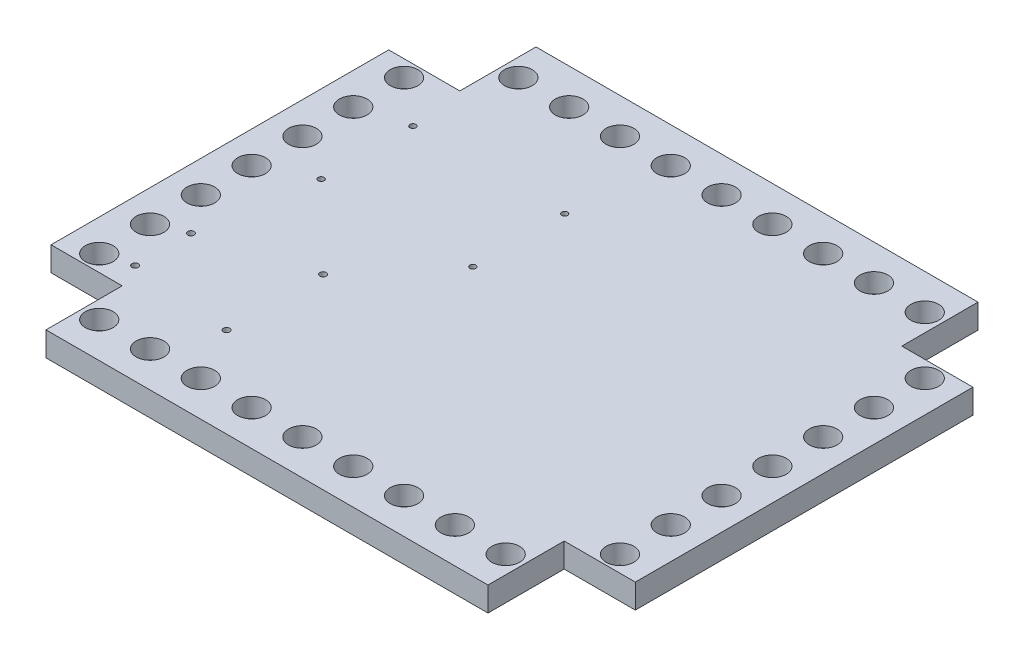
SolidWorks part; units mm, degrees
material "PA Type 6"
ref_plane "Front Plane" through (0, 0, 0) normal (0, 0, 1) x (1, 0, 0)
ref_plane "Top Plane" through (0, 0, 0) normal (0, 1, 0) x (1, 0, 0)
ref_plane "Right Plane" through (0, 0, 0) normal (1, 0, 0) x (0, 0, -1)
sketch "Sketch1" plane through (0, 0, 0) normal (0, 1, 0) x (1, 0, 0)
  line L1 (146.05, 122.5) -> (-146.05, 122.5)
  line L2 (146.05, 122.5) -> (146.05, -122.5)
  line L3 (146.05, -122.5) -> (-146.05, -122.5)
  line L4 (-146.05, 122.5) -> (-146.05, -122.5)
  line L5 (146.05, 122.5) -> (-146.05, -122.5) construction
  line L6 (146.05, -122.5) -> (-146.05, 122.5) construction
  point P0 (0, 0)
  dimension "D1" = 245
  dimension "D2" = 292.1
extrude "Boss-Extrude1" add sketch "Sketch1" along normal blind 9.652
sketch "Sketch2" plane through (0, 9.652, 0) normal (0, 1, 0) x (1, 0, 0)
  line L1 (146.05, 122.5) -> (-146.05, 122.5) construction
  line L2 (-146.05, 122.5) -> (-146.05, -122.5) construction
  line L3 (-146.05, 84.4) -> (-146.05, 122.5)
  line L4 (-146.05, 122.5) -> (-110.49, 122.5)
  line L5 (0, 122.5) -> (0, -122.5) construction
  line L6 (-146.05, -122.5) -> (146.05, -122.5) construction
  line L7 (-146.05, 0) -> (146.05, 0) construction
  line L8 (146.05, -122.5) -> (146.05, 122.5) construction
  line L9 (146.05, 84.4) -> (146.05, 122.5)
  line L11 (146.05, 122.5) -> (110.49, 122.5)
  line L13 (146.05, -122.5) -> (110.49, -122.5)
  line L14 (146.05, -84.4) -> (146.05, -122.5)
  line L15 (-146.05, -84.4) -> (-146.05, -122.5)
  line L17 (-146.05, -122.5) -> (-110.49, -122.5)
  line L18 (-110.49, 122.5) -> (-110.49, 84.4)
  line L19 (-110.49, 84.4) -> (-146.05, 84.4)
  line L20 (110.49, 122.5) -> (110.49, 84.4)
  line L21 (110.49, 84.4) -> (146.05, 84.4)
  line L22 (110.49, -84.4) -> (146.05, -84.4)
  line L23 (110.49, -122.5) -> (110.49, -84.4)
  line L24 (-110.49, -122.5) -> (-110.49, -84.4)
  line L25 (-110.49, -84.4) -> (-146.05, -84.4)
  dimension "D1" = 38.1
  dimension "D2" = 35.56
extrude "Cut-Extrude2" cut sketch "Sketch2" against normal through all
hole_wizard "35/64 (0.54688) Diameter Hole1" positions "Sketch5" profile "Sketch6" hole size "35/64" standard "ANSI Inch" end condition through all
sketch "Sketch5" plane through (0, 9.652, 0) normal (0, 1, 0) x (1, 0, 0)
  line L0 (0, 122.5) -> (0, 0) construction
  line L1 (110.49, 122.5) -> (-110.49, 122.5) construction
  line L2 (0, 0) -> (-146.05, 0) construction
  line L3 (-146.05, 84.4) -> (-146.05, -84.4) construction
  line L4 (0, 104.775) -> (-130.175, 104.775) construction
  line L5 (-130.175, 104.775) -> (-130.175, 0) construction
  point P21 (-25.4, 104.775)
  point P27 (0, 104.775)
  point P30 (-130.175, 0)
  point P35 (-50.8, 104.775)
  point P37 (-76.2, 104.775)
  point P48 (76.2, 104.775)
  point P49 (50.8, 104.775)
  point P50 (25.4, 104.775)
  point P51 (76.2, -104.775)
  point P52 (50.8, -104.775)
  point P53 (25.4, -104.775)
  point P54 (0, -104.775)
  point P55 (-25.4, -104.775)
  point P56 (-50.8, -104.775)
  point P57 (-76.2, -104.775)
  point P60 (-130.175, 25.4)
  point P62 (-130.175, 50.8)
  point P65 (-130.175, -50.8)
  point P66 (-130.175, -25.4)
  point P67 (130.175, -50.8)
  point P68 (130.175, -25.4)
  point P69 (130.175, 0)
  point P70 (130.175, 25.4)
  point P71 (130.175, 50.8)
  point P72 (-130.175, 76.2)
  point P75 (130.175, 76.2)
  point P76 (130.175, -76.2)
  point P77 (-130.175, -76.2)
  point P78 (-101.6, 104.775)
  point P81 (101.6, 104.775)
  point P82 (101.6, -104.775)
  point P83 (-101.6, -104.775)
  dimension "D1" = 104.775
  dimension "D2" = 130.175
  dimension "D3" = 25.4
  dimension "D4" = 50.8
  dimension "D5" = 76.2
  dimension "D6" = 25.4
  dimension "D7" = 50.8
  dimension "D8" = 76.2
  dimension "D9" = 101.6
sketch "Sketch6" plane through (-101.6, 9.652, 104.775) normal (1, 0, 0) x (0, 0, 1)
  line L0 (0, 0) -> (0, 9.652)
  line L1 (0, 9.652) -> (6.9454, 9.652)
  line L2 (6.9454, 9.652) -> (6.9454, 0)
  line L5 (6.9454, 0) -> (0, 0)
  line L11 (0, -6.35) -> (0, 107.95) construction
  dimension "Thru Hole Dia." = 13.8908
  dimension "Thru Hole Depth" = 9.652
sketch "Sketch7" plane through (0, 9.652, 0) normal (0, 1, 0) x (1, 0, 0)
  line L0 (-116.05, -26.66) -> (-116.05, -80) construction
  line L1 (-116.05, -80) -> (-65.25, -80) construction
  line L2 (-65.25, -80) -> (-65.25, -26.66) construction
  line L3 (-65.25, -26.66) -> (-116.05, -26.66) construction
  line L4 (-146.05, 84.4) -> (-146.05, -84.4) construction
  line L5 (-110.49, -122.5) -> (110.49, -122.5) construction
  circle A0 centre (-116.05, -44.44) radius 1.6
  circle A1 centre (-116.05, -72.38) radius 1.6
  circle A4 centre (-65.25, -77.46) radius 1.6
  circle A5 centre (-65.25, -29.2) radius 1.6
  point P8 (-116.05, -72.38)
  point P9 (-116.05, -44.44)
  dimension "D7" = 3.2
  dimension "D8" = 3.2
  dimension "D9" = 2.54
  dimension "D10" = 2.54
  dimension "D11" = 3.2
  dimension "D12" = 3.2
  dimension "D1" = 53.34
  dimension "D2" = 50.8
  dimension "D3" = 30
  dimension "D4" = 42.5
  dimension "D5" = 45.72
  dimension "D6" = 17.78
extrude "Cut-Extrude3" cut sketch "Sketch7" along direction (0, -1, 0) on the side against the normal blind 22.5 and the other way through all
sketch "Sketch8" plane through (0, 9.652, 0) normal (0, 1, 0) x (1, 0, 0)
  line L0 (-109.05, 58.5) -> (-108.05, 58.5) construction
  line L1 (-29.05, 9.5) -> (-109.05, 9.5) construction
  line L2 (-29.05, 9.5) -> (-29.05, 59.5) construction
  line L3 (-29.05, 59.5) -> (-109.05, 59.5) construction
  line L4 (-109.05, 9.5) -> (-109.05, 59.5) construction
  line L5 (-29.05, 9.5) -> (-109.05, 59.5) construction
  line L6 (-29.05, 59.5) -> (-109.05, 9.5) construction
  line L7 (-108.05, 58.5) -> (-108.05, 59.5) construction
  line L8 (-108.05, 58.5) -> (-106.9893, 57.4393) construction
  line L9 (-146.05, 84.4) -> (-146.05, -84.4) construction
  line L10 (110.49, 122.5) -> (-110.49, 122.5) construction
  line L11 (-69.05, 34.5) -> (-69.05, 59.5) construction
  line L12 (-69.05, 34.5) -> (-109.05, 34.5) construction
  point P0 (-69.05, 34.5)
  point P15 (-31.1107, 57.4393)
  point P17 (-107.4072, 57.8572)
  point P18 (-31.1107, 11.5607)
  point P19 (-106.9893, 11.5607)
  dimension "D1" = 80
  dimension "D2" = 50
  dimension "D3" = 1
  dimension "D4" = 1
  dimension "D5" = 135
  dimension "D6" = 37
  dimension "D7" = 63
  dimension "D8" = 1.5
hole_wizard "#32 (0.116) Diameter Hole2" positions "Sketch9" profile "Sketch10" hole size "#32" standard "ANSI Inch" end condition through all
sketch "Sketch9" plane through (0, 9.652, 0) normal (0, 1, 0) x (1, 0, 0)
  point P0 (-106.9893, 57.4393)
  point P3 (-31.1107, 57.4393)
  point P6 (-31.1107, 11.5607)
  point P9 (-106.9893, 11.5607)
sketch "Sketch10" plane through (-106.9893, 9.652, -57.4393) normal (1, 0, 0) x (0, 0, 1)
  line L0 (0, 0) -> (0, 9.652)
  line L1 (0, 9.652) -> (1.4732, 9.652)
  line L2 (1.4732, 9.652) -> (1.4732, 0)
  line L5 (1.4732, 0) -> (0, 0)
  line L11 (0, -6.35) -> (0, 107.95) construction
  dimension "Thru Hole Dia." = 2.9464
  dimension "Thru Hole Depth" = 9.652
sketch "Sketch11" plane through (0, 9.652, 0) normal (0, 1, 0) x (1, 0, 0)
  line L0 (-146.05, 84.4) -> (-110.49, 84.4)
  line L1 (-110.49, 84.4) -> (-110.49, 122.5)
  line L2 (-110.49, 122.5) -> (110.49, 122.5)
  line L3 (110.49, 122.5) -> (110.49, 84.4)
  line L4 (110.49, 84.4) -> (146.05, 84.4)
  line L5 (146.05, 84.4) -> (146.05, -84.4)
  line L6 (146.05, -84.4) -> (110.49, -84.4)
  line L7 (110.49, -84.4) -> (110.49, -122.5)
  line L8 (110.49, -122.5) -> (-110.49, -122.5)
  line L9 (-110.49, -122.5) -> (-110.49, -84.4)
  line L10 (-110.49, -84.4) -> (-146.05, -84.4)
  line L11 (-146.05, -84.4) -> (-146.05, 84.4)
sketch "Sketch12" plane through (0, 0, 0) normal (0, -1, 0) x (1, 0, 0)
  line L0 (-146.05, 84.4) -> (-110.49, 84.4)
  line L1 (-110.49, 84.4) -> (-110.49, 122.5)
  line L2 (-110.49, 122.5) -> (110.49, 122.5)
  line L3 (110.49, 122.5) -> (110.49, 84.4)
  line L4 (110.49, 84.4) -> (146.05, 84.4)
  line L5 (146.05, 84.4) -> (146.05, -84.4)
  line L6 (146.05, -84.4) -> (110.49, -84.4)
  line L7 (110.49, -84.4) -> (110.49, -122.5)
  line L8 (110.49, -122.5) -> (-110.49, -122.5)
  line L9 (-110.49, -122.5) -> (-110.49, -84.4)
  line L10 (-110.49, -84.4) -> (-146.05, -84.4)
  line L11 (-146.05, -84.4) -> (-146.05, 84.4)
  line L12 (0, 122.5) -> (0, 0) construction
  line L13 (0, 0) -> (-146.05, 0) construction
  circle A0 centre (-65.25, 77.46) radius 1.6
  circle A1 centre (-116.05, 72.38) radius 1.6
  circle A2 centre (-116.05, 44.44) radius 1.6
  circle A3 centre (-65.25, 29.2) radius 1.6
  circle A4 centre (-106.9893, -11.5607) radius 1.4732
  circle A5 centre (-31.1107, -11.5607) radius 1.4732
  circle A6 centre (-31.1107, -57.4393) radius 1.4732
  circle A7 centre (-106.9893, -57.4393) radius 1.4732
  circle A8 centre (-101.6, 104.775) radius 3.175
  circle A9 centre (-76.2, 104.775) radius 3.175
  circle A10 centre (-50.8, 104.775) radius 3.175
  circle A11 centre (-25.4, 104.775) radius 3.175
  circle A12 centre (0, 104.775) radius 3.175
  circle A13 centre (25.4, 104.775) radius 3.175
  circle A14 centre (50.8, 104.775) radius 3.175
  circle A15 centre (76.2, 104.775) radius 3.175
  circle A16 centre (101.6, 104.775) radius 3.175
  circle A17 centre (101.6, -104.775) radius 3.175
  circle A18 centre (76.2, -104.775) radius 3.175
  circle A19 centre (50.8, -104.775) radius 3.175
  circle A20 centre (25.4, -104.775) radius 3.175
  circle A21 centre (0, -104.775) radius 3.175
  circle A22 centre (-25.4, -104.775) radius 3.175
  circle A23 centre (-50.8, -104.775) radius 3.175
  circle A24 centre (-76.2, -104.775) radius 3.175
  circle A25 centre (-101.6, -104.775) radius 3.175
  circle A26 centre (-130.175, 76.2) radius 3.175
  circle A27 centre (-130.175, 50.8) radius 3.175
  circle A28 centre (-130.175, 25.4) radius 3.175
  circle A29 centre (-130.175, 0) radius 3.175
  circle A30 centre (-130.175, -25.4) radius 3.175
  circle A31 centre (-130.175, -50.8) radius 3.175
  circle A32 centre (-130.175, -76.2) radius 3.175
  circle A33 centre (130.175, -76.2) radius 3.175
  circle A34 centre (130.175, -50.8) radius 3.175
  circle A35 centre (130.175, -25.4) radius 3.175
  circle A36 centre (130.175, 0) radius 3.175
  circle A37 centre (130.175, 25.4) radius 3.175
  circle A38 centre (130.175, 50.8) radius 3.175
  circle A39 centre (130.175, 76.2) radius 3.175
  dimension "D1" = 3.2
  dimension "D2" = 3.2
  dimension "D3" = 3.2
  dimension "D4" = 3.2
  dimension "D5" = 2.9464
  dimension "D6" = 2.9464
  dimension "D7" = 2.9464
  dimension "D8" = 2.9464
  dimension "D9" = 6.35
  dimension "D12" = 6.35
  dimension "D11" = 9
  dimension "D13" = 7
extrude "Boss-Extrude3" add sketch "Sketch12" along normal blind 2.5
extrude "Boss-Extrude4" add sketch "Sketch12<2>" along normal blind 2.5
sketch "Sketch12<2>" plane through (0, 0, 0) normal (0, -1, 0) x (1, 0, 0) same geometry as "Sketch12"
